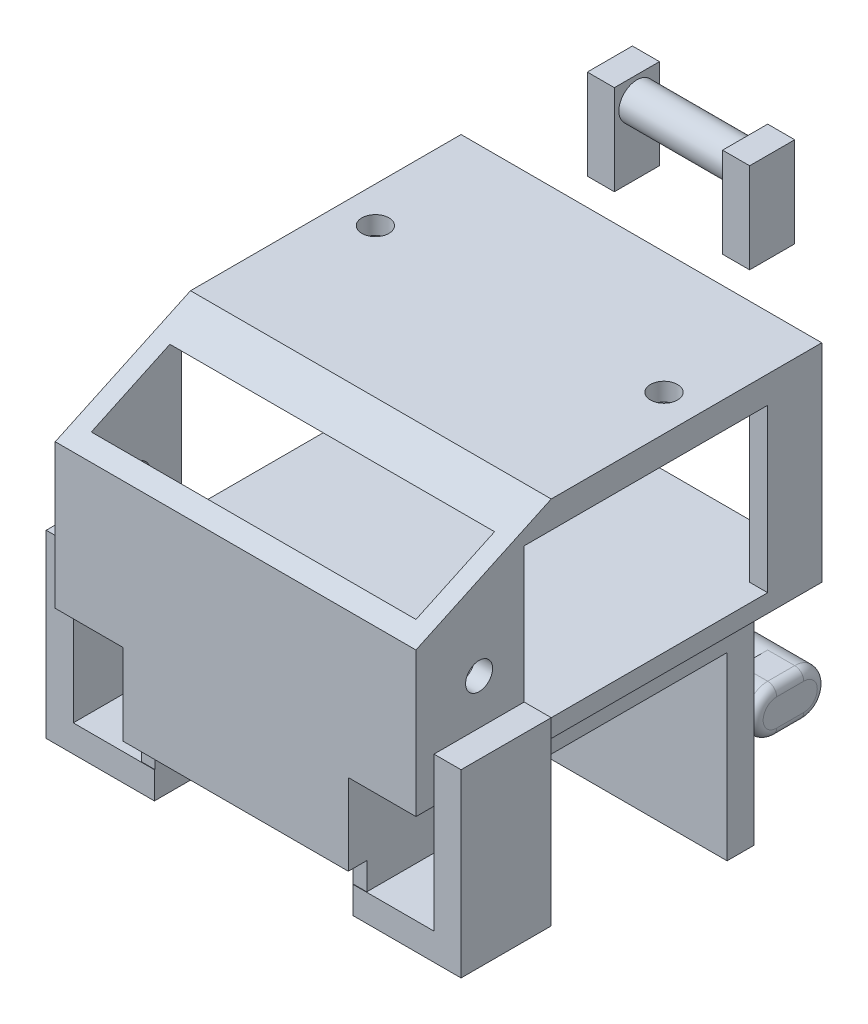
SolidWorks part; units mm, degrees
ref_plane "正面" through (0, 0, 0) normal (0, 0, 1) x (1, 0, 0)
ref_plane "平面" through (0, 0, 0) normal (0, 1, 0) x (1, 0, 0)
ref_plane "右側面" through (0, 0, 0) normal (1, 0, 0) x (0, 0, -1)
sketch "ｽｹｯﾁ1" plane through (0, 0, 0) normal (0, 1, 0) x (1, 0, 0)
  line L1 (0, 0) -> (25, 0)
  line L2 (0, 0) -> (0, 42)
  line L3 (0, 42) -> (25, 42)
  line L4 (25, 0) -> (25, 42)
  dimension "D1" = 25
  dimension "D2" = 42
extrude "ﾎﾞｽ - 押し出し1" add sketch "ｽｹｯﾁ1" along normal blind 9
sketch "ｽｹｯﾁ2" plane through (0, 0, -42) normal (0, 0, -1) x (-1, 0, 0)
  line L1 (-25, 9) -> (0, 9)
  line L2 (-25, 9) -> (-25, -20)
  line L3 (-25, -20) -> (0, -20)
  line L4 (0, 9) -> (0, -20)
  dimension "D1" = 29
extrude "ﾎﾞｽ - 押し出し2" add sketch "ｽｹｯﾁ2" along normal blind 3
sketch "ｽｹｯﾁ3" plane through (0, 9, 0) normal (0, 1, 0) x (1, 0, 0)
  line L1 (-7.5, 0) -> (32.5, 0)
  line L2 (-7.5, 0) -> (-7.5, 45)
  line L3 (-7.5, 45) -> (32.5, 45)
  line L4 (32.5, 0) -> (32.5, 45)
  line L5 (0, 0) -> (25, 0) construction
  line L6 (0, 45) -> (25, 45) construction
  line L7 (0, 45) -> (0, 0) construction
  dimension "D1" = 40
  dimension "D2" = 7.5
extrude "ﾎﾞｽ - 押し出し3" add sketch "ｽｹｯﾁ3" along normal blind 23
sketch "ｽｹｯﾁ4" plane through (0, 0, -45) normal (0, 0, -1) x (-1, 0, 0)
  line L0 (-32.5, 32) -> (7.5, 32) construction
  line L1 (5.5, 30) -> (-30.5, 30)
  line L2 (5.5, 30) -> (5.5, 11)
  line L3 (5.5, 11) -> (-30.5, 11)
  line L4 (-30.5, 30) -> (-30.5, 11)
  line L5 (7.5, 32) -> (7.5, 9) construction
  line L6 (-32.5, 32) -> (-32.5, 9) construction
  line L7 (0, 9) -> (7.5, 9) construction
  dimension "D1" = 2
  dimension "D2" = 2
  dimension "D3" = 2
  dimension "D4" = 2
extrude "ｶｯﾄ - 押し出し1" cut sketch "ｽｹｯﾁ4" against normal blind 43
sketch "ｽｹｯﾁ6" plane through (32.5, 0, 0) normal (1, 0, 0) x (0, 0, -1)
  line L0 (42, 0) -> (42, -20) construction
  line L1 (2, -6) -> (12, -6)
  line L2 (2, -6) -> (2, 14)
  line L3 (2, 14) -> (12, 14)
  line L4 (12, -6) -> (12, 14)
  line L5 (0, 9) -> (45, 9) construction
  dimension "D1" = 30
  dimension "D2" = 20
  dimension "D3" = 10
  dimension "D4" = 15
extrude "ﾎﾞｽ - 押し出し4" add sketch "ｽｹｯﾁ6" along normal blind 3
sketch "ｽｹｯﾁ7" plane through (0, -6, 0) normal (0, -1, 0) x (1, 0, 0)
  line L0 (35.5, -2) -> (32.5, -2) construction
  line L1 (32.5, -12) -> (23.5, -12)
  line L2 (32.5, -12) -> (32.5, -2)
  line L3 (32.5, -2) -> (23.5, -2)
  line L4 (23.5, -12) -> (23.5, -2)
  dimension "D1" = 9
extrude "ﾎﾞｽ - 押し出し5" add sketch "ｽｹｯﾁ7" against normal blind 3
ref_plane "平面1" through (12.5, 0, 0) normal (1, 0, 0) x (0, 0, -1)
mirror "ﾐﾗｰ1" about plane through (12.5, 0, 0) normal (1, 0, 0) of "ﾎﾞｽ - 押し出し4", "ﾎﾞｽ - 押し出し5"
sketch "ｽｹｯﾁ8" plane through (0, 32, 0) normal (0, 1, 0) x (1, 0, 0)
  line L0 (12.5, -15.95) -> (12.5, 15.95) construction
  line L1 (3.5, 53) -> (6.5, 53)
  line L2 (3.5, 53) -> (3.5, 48)
  line L3 (3.5, 48) -> (6.5, 48)
  line L4 (6.5, 53) -> (6.5, 48)
  line L5 (21.5, 48) -> (18.5, 48)
  line L6 (18.5, 53) -> (18.5, 48)
  line L7 (21.5, 53) -> (18.5, 53)
  line L8 (21.5, 53) -> (21.5, 48)
  line L10 (32.5, 45) -> (-7.5, 45) construction
  dimension "D1" = 5
  dimension "D2" = 3
  dimension "D3" = 12
  dimension "D4" = 8
extrude "ﾎﾞｽ - 押し出し6" add sketch "ｽｹｯﾁ8" along normal blind 10
sketch "ｽｹｯﾁ9" plane through (6.5, 0, 0) normal (1, 0, 0) x (0, 0, -1)
  line L0 (48, 42) -> (48, 32) construction
  line L1 (48, 42) -> (53, 42) construction
  circle A0 centre (50.5, 39.5) radius 2
  dimension "D1" = 4
  dimension "D2" = 2.5
  dimension "D3" = 2.5
extrude "ﾎﾞｽ - 押し出し7" add sketch "ｽｹｯﾁ9" along normal up to next (12 mm away)
sketch "ｽｹｯﾁ10" plane through (-7.5, 0, 0) normal (-1, 0, 0) x (0, 0, 1)
  line L0 (-2, 9) -> (0, 9) construction
  line L1 (0, 32) -> (0, 9) construction
  circle A0 centre (-7, 19) radius 1.5
  dimension "D1" = 3
  dimension "D2" = 10
  dimension "D3" = 7
extrude "ｶｯﾄ - 押し出し2" cut sketch "ｽｹｯﾁ10" against normal through all
sketch "ｽｹｯﾁ11" plane through (0, 0, -45) normal (0, 0, -1) x (-1, 0, 0)
  line L1 (-25, -20) -> (0, -20) construction
  line L2 (-12.5, 15.95) -> (-12.5, -15.95) construction
  circle A0 centre (-12.5, -10) radius 2.5
  dimension "D1" = 5
  dimension "D2" = 10
extrude "ﾎﾞｽ - 押し出し8" add sketch "ｽｹｯﾁ11" along normal blind 9
sketch "ｽｹｯﾁ12" plane through (12.5, 0, 0) normal (1, 0, 0) x (0, 0, -1)
  line L0 (45, -12.5) -> (45, -7.5) construction
  line L2 (45, -12.5) -> (54, -12.5) construction
  circle A0 centre (52, -10) radius 2.5
  dimension "D1" = 5
  dimension "D2" = 7
  dimension "D3" = 2.5
extrude "ﾎﾞｽ - 押し出し9" add sketch "ｽｹｯﾁ12" along normal blind 7
sketch "ｽｹｯﾁ13" plane through (19.5, 0, 0) normal (1, 0, 0) x (0, 0, -1)
  line L0 (52, -10) -> (49, -10) construction
  line L1 (52, -12.5) -> (49, -12.5)
  line L2 (52, -7.5) -> (49, -7.5)
  arc A0 (52, -12.5) -> (52, -7.5) centre (52, -10) ccw
  arc A1 (49, -7.5) -> (49, -12.5) centre (49, -10) ccw
  circle A2 centre (52, -10) radius 2.5 construction
  point P2 (50.5, -10)
  dimension "D1" = 2.5
  dimension "D2" = 3
extrude "ﾎﾞｽ - 押し出し10" add sketch "ｽｹｯﾁ13" along normal blind 4
fillet "ﾌｨﾚｯﾄ1" radius 1 4 edges at (23.5, -12.5, -50.5) (23.5, -10, -46.5) (23.5, -7.5, -50.5) (23.5, -10, -54.5)
mirror "ﾐﾗｰ2" about plane through (12.5, 0, 0) normal (1, 0, 0) of "ﾌｨﾚｯﾄ1", "ﾎﾞｽ - 押し出し10", "ﾎﾞｽ - 押し出し9"
sketch "ｽｹｯﾁ14" plane through (-7.5, 0, 0) normal (-1, 0, 0) x (0, 0, 1)
  line L0 (-15, 32) -> (0, 25)
  line L1 (-45, 32) -> (0, 32) construction
  line L2 (0, 32) -> (0, 9) construction
  line L3 (0, 25) -> (0, 32)
  line L4 (0, 32) -> (-15, 32)
  dimension "D1" = 15
  dimension "D2" = 7
extrude "ｶｯﾄ - 押し出し3" cut sketch "ｽｹｯﾁ14" against normal through all
sketch "ｽｹｯﾁ15" plane through (-7.5, 0, 0) normal (-1, 0, 0) x (0, 0, 1)
  line L0 (-45, 9) -> (-53, 32)
  line L1 (-53, 32) -> (-45, 32)
  line L2 (-45, 32) -> (-45, 9)
  dimension "D1" = 8
sketch "ｽｹｯﾁ19" plane through (30.5, 0, 0) normal (-1, 0, 0) x (0, 0, 1)
  line L0 (-2, 11) -> (-45, 11) construction
  line L1 (-39, 11) -> (-12, 11)
  line L2 (-39, 11) -> (-39, 29)
  line L3 (-39, 29) -> (-12, 29)
  line L4 (-12, 11) -> (-12, 29)
  line L5 (-2, 25.9333) -> (-2, 11) construction
  dimension "D1" = 27
  dimension "D2" = 10
  dimension "D3" = 18
extrude "ｶｯﾄ - 押し出し5" cut sketch "ｽｹｯﾁ19" against normal through all both and the other way through all
sketch "ｽｹｯﾁ20" plane through (0, 32, 0) normal (0, 1, 0) x (1, 0, 0)
  line L0 (-7.5, 45) -> (-7.5, 15) construction
  line L1 (32.5, 15) -> (32.5, 45) construction
  line L2 (3.5, 48) -> (6.5, 48) construction
  line L3 (18.5, 48) -> (21.5, 48) construction
  circle A0 centre (-3.5, 31.5) radius 1.5
  circle A1 centre (28.5, 31.5) radius 1.5
  dimension "D1" = 3
  dimension "D2" = 3
  dimension "D3" = 4
  dimension "D4" = 4
  dimension "D5" = 16.5
  dimension "D6" = 16.5
extrude "ｶｯﾄ - 押し出し6" cut sketch "ｽｹｯﾁ20" against normal blind 10 and the other way through all
sketch "ｽｹｯﾁ21" plane through (0, 30, 0) normal (0, -1, 0) x (1, 0, 0)
  line L0 (-5.5, -45) -> (30.5, -45) construction
  line L1 (-5.5, -10.7143) -> (-5.5, -45) construction
  line L2 (22.5, -45) -> (19.5, -45)
  line L3 (22.5, -45) -> (22.5, -40)
  line L4 (22.5, -40) -> (19.5, -40)
  line L5 (19.5, -45) -> (19.5, -40)
  line L6 (5.5, -45) -> (2.5, -45)
  line L7 (5.5, -45) -> (5.5, -40)
  line L8 (5.5, -40) -> (2.5, -40)
  line L9 (2.5, -45) -> (2.5, -40)
  dimension "D1" = 3
  dimension "D2" = 5
  dimension "D3" = 3
  dimension "D4" = 5
  dimension "D5" = 8
  dimension "D6" = 8
extrude "ﾎﾞｽ - 押し出し11" add sketch "ｽｹｯﾁ21" along normal blind 10
sketch "ｽｹｯﾁ22" plane through (19.5, 0, 0) normal (-1, 0, 0) x (0, 0, 1)
  line L0 (-40, 20) -> (-45, 20) construction
  line L1 (-40, 20) -> (-40, 30) construction
  circle A0 centre (-42.5, 22.5) radius 2.5
  dimension "D1" = 5
  dimension "D2" = 2.5
  dimension "D3" = 2.5
extrude "ﾎﾞｽ - 押し出し12" add sketch "ｽｹｯﾁ22" along normal up to next
sketch "ｽｹｯﾁ23" plane through (1.5, 0, 0) normal (1, 0, 0) x (0, 0, -1)
  line L0 (42, 0) -> (0, 0) construction
  line L1 (12, -3) -> (2.0458, -3)
  line L2 (12, -3) -> (12, 0)
  line L3 (12, 0) -> (2.0458, 0)
  line L4 (2.0458, -3) -> (2.0458, 0)
extrude "ﾎﾞｽ - 押し出し13" add sketch "ｽｹｯﾁ23" against normal blind 1.5
mirror "ﾐﾗｰ3" about plane through (12.5, 0, 0) normal (1, 0, 0) of "ﾎﾞｽ - 押し出し13"
